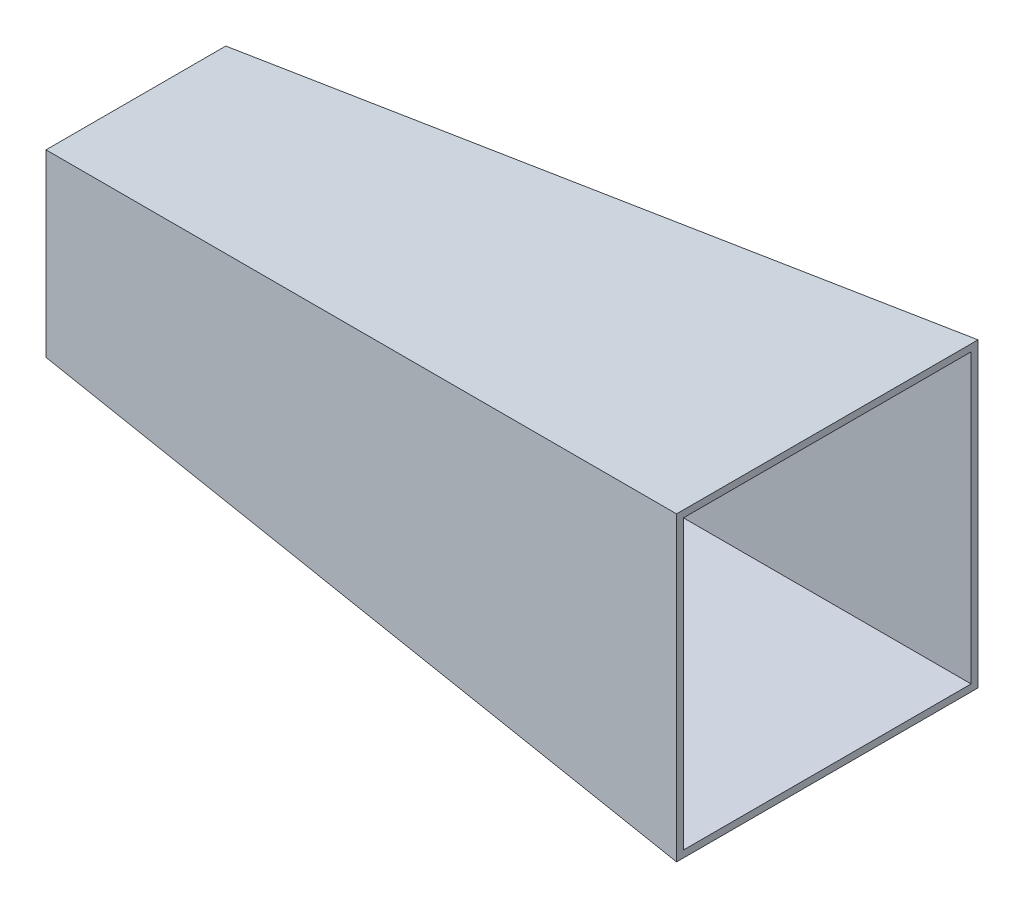
SolidWorks part; units mm, degrees
ref_plane "Front Plane" through (0, 0, 0) normal (0, 0, 1) x (1, 0, 0)
ref_plane "Top Plane" through (0, 0, 0) normal (0, 1, 0) x (1, 0, 0)
ref_plane "Right Plane" through (0, 0, 0) normal (1, 0, 0) x (0, 0, -1)
sketch "Sketch1" plane through (0, 0, 0) normal (1, 0, 0) x (0, 0, -1)
  line L1 (-60, 60) -> (60, 60)
  line L2 (-60, 60) -> (-60, -60)
  line L3 (-60, -60) -> (60, -60)
  line L4 (60, 60) -> (60, -60)
  line L5 (-60, 60) -> (60, -60) construction
  line L6 (-60, -60) -> (60, 60) construction
  line L7 (-65, 65) -> (65, 65)
  line L8 (-65, 65) -> (-65, -65)
  line L9 (-65, -65) -> (65, -65)
  line L10 (65, 65) -> (65, -65)
  line L11 (-65, 65) -> (65, -65) construction
  line L12 (-65, -65) -> (65, 65) construction
  point P0 (0, 0)
  point P6 (0, 0)
  dimension "D1" = 120
  dimension "D2" = 120
  dimension "D3" = 5
  dimension "D4" = 5
ref_plane "Plane1" through (500, 0, 0) normal (1, 0, 0) x (0, 0, -1)
sketch "Sketch2" plane through (500, 0, 0) normal (1, 0, 0) x (0, 0, -1)
  line L1 (-104, 104) -> (104, 104)
  line L2 (-104, 104) -> (-104, -104)
  line L3 (-104, -104) -> (104, -104)
  line L4 (104, 104) -> (104, -104)
  line L5 (-104, 104) -> (104, -104) construction
  line L6 (-104, -104) -> (104, 104) construction
  line L7 (-109, 109) -> (109, 109)
  line L8 (-109, 109) -> (-109, -109)
  line L9 (-109, -109) -> (109, -109)
  line L10 (109, 109) -> (109, -109)
  line L11 (-109, 109) -> (109, -109) construction
  line L12 (-109, -109) -> (109, 109) construction
  point P0 (0, 0)
  point P6 (0, 0)
  dimension "D1" = 208
  dimension "D2" = 208
  dimension "D3" = 5
  dimension "D4" = 5
loft "Loft1" add section "Sketch1" section "Sketch2" connector at (0, 65, -65) connector at (500, 109, -109)
loft "Cut-Loft1" cut section "Sketch1<3>" section "Sketch2<3>" connector at (0, 60, -60) connector at (500, 104, -104)
sketch "Sketch1<3>" plane through (0, 0, 0) normal (1, 0, 0) x (0, 0, -1) same geometry as "Sketch1"
sketch "Sketch2<3>" plane through (500, 0, 0) normal (1, 0, 0) x (0, 0, -1) same geometry as "Sketch2"
